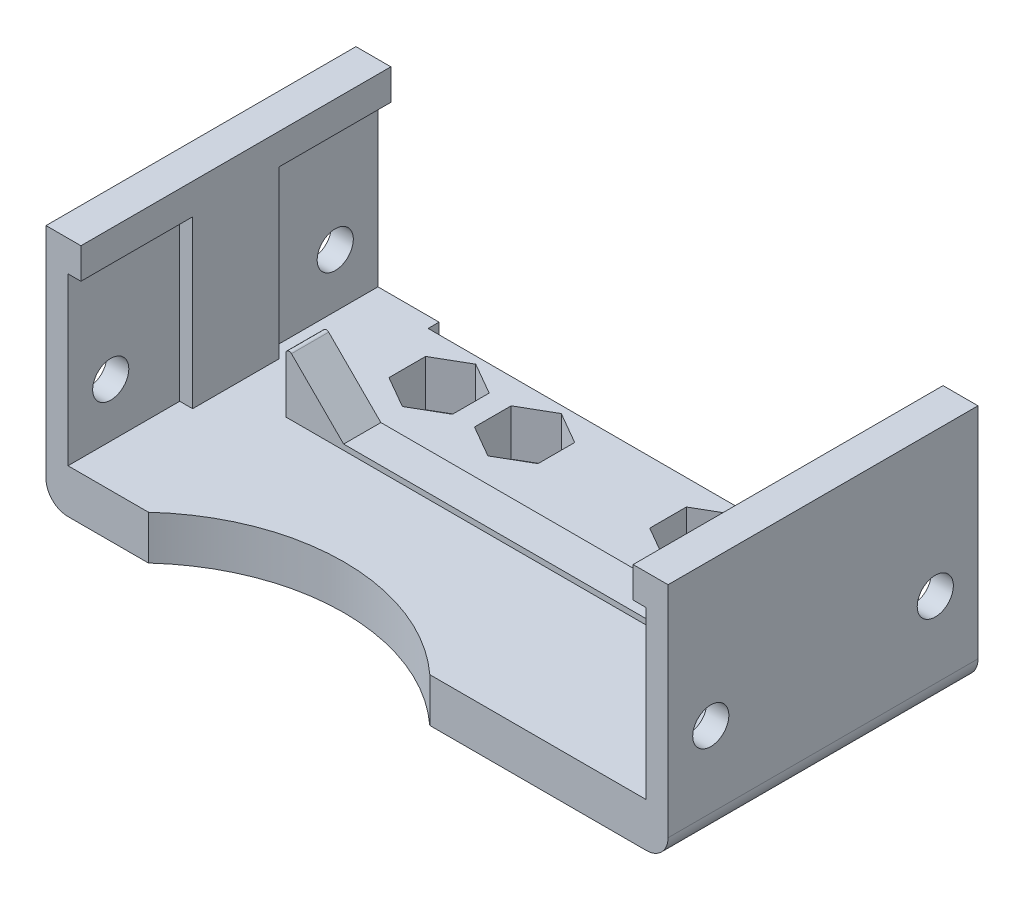
SolidWorks part; units mm, degrees
ref_plane "Front Plane" through (0, 0, 0) normal (0, 0, 1) x (1, 0, 0)
ref_plane "Top Plane" through (0, 0, 0) normal (0, 1, 0) x (1, 0, 0)
ref_plane "Right Plane" through (0, 0, 0) normal (1, 0, 0) x (0, 0, -1)
sketch "Sketch1" plane through (0, 0, 0) normal (0, 0, 1) x (1, 0, 0)
  line L0 (0, 22.01) -> (3.19, 22.01)
  line L1 (0, 22.01) -> (0, 2)
  line L2 (2, 0) -> (54.8, 0)
  line L3 (56.8, 22.01) -> (56.8, 2)
  line L18 (53.61, 22.01) -> (56.8, 22.01)
  line L54 (53.61, 4.02) -> (53.61, 22.01)
  line L55 (3.19, 22.01) -> (3.19, 4.02)
  line L57 (3.19, 4.02) -> (53.61, 4.02)
  arc A0 (54.8, 0) -> (56.8, 2) centre (54.8, 2) ccw
  arc A1 (0, 2) -> (2, 0) centre (2, 2) ccw
extrude "Boss-Extrude1" add sketch "Sketch1" along normal blind 28.3
sketch "Sketch2" plane through (0, 0, 0) normal (0, 0, 1) x (1, 0, 0)
  line L0 (2.01, 19.2) -> (54.79, 19.2)
  line L1 (2.01, 19.2) -> (2.01, 4.02)
  line L2 (2.01, 4.02) -> (54.79, 4.02)
  line L3 (54.79, 19.2) -> (54.79, 4.02)
extrude "Cut-Extrude1" cut sketch "Sketch2" along normal blind 10.2
extrude "Cut-Extrude2" cut sketch "Sketch2<2>" against normal blind 10.2 from surface starting at face at (28.4, 9.9252, 28.3)
sketch "Sketch2<2>" plane through (0, 0, 0) normal (0, 0, 1) x (1, 0, 0) same geometry as "Sketch2"
sketch "Sketch3" plane through (0, 0, 0) normal (-1, 0, 0) x (0, 0, 1)
  circle A0 centre (3.9, 8.91) radius 1.65
  circle A1 centre (24.4, 8.91) radius 1.65
extrude "Cut-Extrude3" cut sketch "Sketch3" against normal up to surface (56.8 mm away) up to face at (56.8, 12.005, 14.15)
sketch "Sketch4" plane through (0, 0, 0) normal (0, 0, 1) x (1, 0, 0)
  line L0 (8.6121, 9.286) -> (13.3782, 4.52)
  line L3 (8.1, 4.02) -> (48.7, 4.02)
  line L5 (13.3782, 4.52) -> (43.4218, 4.52)
  line L6 (43.4218, 4.52) -> (48.1879, 9.286)
  line L12 (8.1, 4.02) -> (8.1, 9.0739)
  line L13 (48.7, 4.02) -> (48.7, 9.0739)
  arc A0 (48.7, 9.0739) -> (48.1879, 9.286) centre (48.4, 9.0739) ccw
  arc A1 (8.1, 9.0739) -> (8.6121, 9.286) centre (8.4, 9.0739) cw
extrude "Boss-Extrude2" add sketch "Sketch4" along normal blind 3.4 from offset 11.1
sketch "Sketch5" plane through (0, 0, 0) normal (0, -1, 0) x (1, 0, 0)
  line L4 (35.0452, 28.3) -> (9.3548, 28.3)
  arc A0 (9.3548, 28.3) -> (35.0452, 28.3) centre (22.2, 42.3) ccw
extrude "Cut-Extrude4" cut sketch "Sketch5" against normal up to surface (4.02 mm away) up to face at (28.4, 4.02, 12.8)
sketch "Sketch6" plane through (0, 0, 0) normal (0, -1, 0) x (1, 0, 0)
  line L52 (32.9, 10) -> (47.71, 10)
  line L55 (9.09, 10) -> (23.9, 10)
  line L64 (7.59, 8.5) -> (7.59, 0)
  line L65 (7.59, 0) -> (25.4, 0)
  line L66 (25.4, 8.5) -> (25.4, 0)
  line L69 (31.4, 8.5) -> (31.4, 0)
  line L70 (31.4, 0) -> (49.21, 0)
  line L71 (49.21, 8.5) -> (49.21, 0)
  circle A6 centre (20.4, 5) radius 1.65
  circle A7 centre (36.4, 5) radius 1.65
  circle A22 centre (12.59, 5) radius 1.65
  circle A23 centre (44.21, 5) radius 1.65
  arc A39 (32.9, 10) -> (31.4, 8.5) centre (32.9, 8.5) ccw
  arc A42 (47.71, 10) -> (49.21, 8.5) centre (47.71, 8.5) cw
  arc A49 (9.09, 10) -> (7.59, 8.5) centre (9.09, 8.5) ccw
  arc A52 (23.9, 10) -> (25.4, 8.5) centre (23.9, 8.5) cw
extrude "Boss-Extrude3" add sketch "Sketch6" along normal blind 3.2
sketch "Sketch8" plane through (0, 4.02, 0) normal (0, -1, 0) x (1, 0, 0)
  line L0 (23.3, 6.6743) -> (20.4, 8.3486)
  line L7 (20.4, 8.3486) -> (17.5, 6.6743)
  line L8 (17.5, 6.6743) -> (17.5, 3.3257)
  line L21 (17.5, 3.3257) -> (20.4, 1.6514)
  line L22 (20.4, 1.6514) -> (23.3, 3.3257)
  line L23 (23.3, 3.3257) -> (23.3, 6.6743)
  line L25 (39.3, 6.6743) -> (36.4, 8.3486)
  line L26 (36.4, 8.3486) -> (33.5, 6.6743)
  line L27 (33.5, 6.6743) -> (33.5, 3.3257)
  line L28 (33.5, 3.3257) -> (36.4, 1.6514)
  line L29 (36.4, 1.6514) -> (39.3, 3.3257)
  line L30 (39.3, 3.3257) -> (39.3, 6.6743)
  line L33 (47.11, 6.6743) -> (44.21, 8.3486)
  line L34 (44.21, 8.3486) -> (41.31, 6.6743)
  line L35 (41.31, 6.6743) -> (41.31, 3.3257)
  line L36 (41.31, 3.3257) -> (44.21, 1.6514)
  line L37 (44.21, 1.6514) -> (47.11, 3.3257)
  line L38 (47.11, 3.3257) -> (47.11, 6.6743)
  line L40 (15.49, 6.6743) -> (12.59, 8.3486)
  line L41 (12.59, 8.3486) -> (9.69, 6.6743)
  line L42 (9.69, 6.6743) -> (9.69, 3.3257)
  line L43 (9.69, 3.3257) -> (12.59, 1.6514)
  line L44 (12.59, 1.6514) -> (15.49, 3.3257)
  line L45 (15.49, 3.3257) -> (15.49, 6.6743)
extrude "Cut-Extrude5" cut sketch "Sketch8" along normal offset from surface (4.22 mm away) 3 up to face at (20.4, -3.2, 3.35)
sketch "Sketch10" plane through (0, 0, 0) normal (0, 0, -1) x (-1, 0, 0)
  line L1 (-7.59, -4.4) -> (-49.21, -4.4)
  line L2 (-7.59, -4.4) -> (-7.59, 4.02)
  line L3 (-7.59, 4.02) -> (-49.21, 4.02)
  line L4 (-49.21, -4.4) -> (-49.21, 4.02)
extrude "Cut-Extrude6" cut sketch "Sketch10" against normal blind 1
